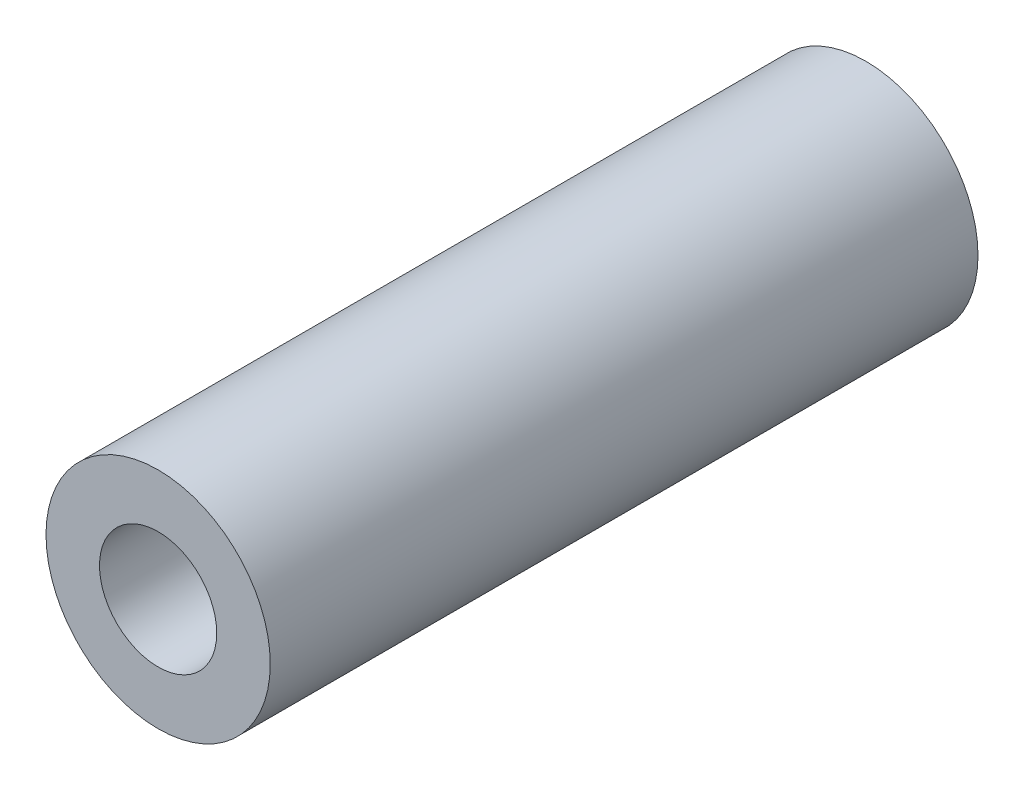
SolidWorks part; units mm, degrees
ref_plane "Front Plane" through (0, 0, 0) normal (0, 0, 1) x (1, 0, 0)
ref_plane "Top Plane" through (0, 0, 0) normal (0, 1, 0) x (1, 0, 0)
ref_plane "Right Plane" through (0, 0, 0) normal (1, 0, 0) x (0, 0, -1)
sketch "Sketch1" plane through (0, 0, 0) normal (0, 0, 1) x (1, 0, 0)
  circle A0 centre (0, 0) radius 2.4892
  circle A1 centre (0, 0) radius 4.7625
  dimension "D1" = 4.9784
  dimension "D2" = 9.525
extrude "Boss-Extrude1" add sketch "Sketch1" along normal mid plane 30.0609
